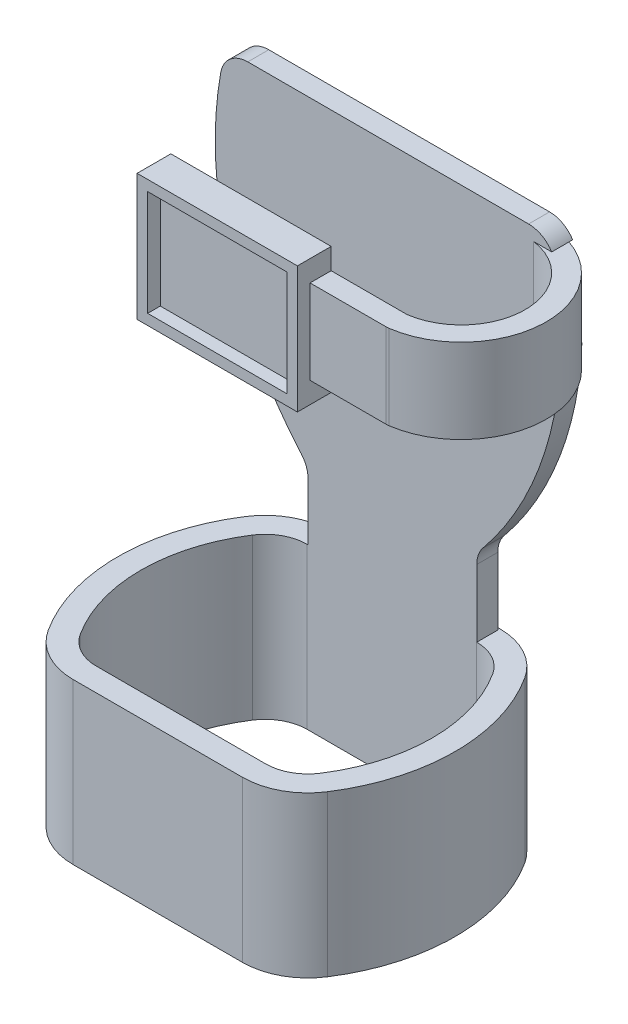
SolidWorks part; units mm, degrees
ref_plane "Alzado" through (0, 0, 0) normal (0, 0, 1) x (1, 0, 0)
ref_plane "Planta" through (0, 0, 0) normal (0, 1, 0) x (1, 0, 0)
ref_plane "Vista lateral" through (0, 0, 0) normal (1, 0, 0) x (0, 0, -1)
sketch "Croquis1" plane through (0, 0, 0) normal (0, 0, 1) x (1, 0, 0)
  line L0 (-15.4785, 127) -> (53.4785, 127)
  line L1 (6.5, 0) -> (33.5, 0)
  line L2 (0, 6.5) -> (0, 51.6048)
  line L3 (0, 130) -> (40, 130)
  line L4 (40, 6.5) -> (40, 53.9643)
  line L5 (40, 130) -> (52.2832, 130)
  line L9 (0, 130) -> (-14.2832, 130)
  line L12 (38, 9) -> (35.8, 9)
  line L13 (38, 9) -> (38, 35)
  line L14 (38, 35) -> (35.8, 35)
  line L15 (35.8, 9) -> (35.8, 35)
  line L16 (2, 9) -> (4.2, 9)
  line L17 (2, 9) -> (2, 35)
  line L18 (2, 35) -> (4.2, 35)
  line L19 (4.2, 9) -> (4.2, 35)
  line L20 (-17.6785, 127) -> (-15.4785, 127)
  line L21 (-17.6785, 127) -> (-17.6785, 101)
  line L22 (-17.6785, 101) -> (-15.4785, 101)
  line L23 (-15.4785, 127) -> (-15.4785, 101)
  line L24 (53.4785, 127) -> (55.6785, 127)
  line L25 (53.4785, 127) -> (53.4785, 101)
  line L26 (53.4785, 101) -> (55.6785, 101)
  line L27 (55.6785, 127) -> (55.6785, 101)
  arc A0 (-20.6785, 124.6623) -> (-1.6158, 55.8937) centre (60, 110) ccw
  arc A2 (41.4689, 58.0799) -> (58.6785, 124.6623) centre (-22, 110) ccw
  arc A3 (33.5, 0) -> (40, 6.5) centre (33.5, 6.5) ccw
  arc A4 (6.5, 0) -> (0, 6.5) centre (6.5, 6.5) cw
  arc A5 (58.6785, 124.6623) -> (52.2832, 130) centre (52.2832, 123.5) ccw
  arc A6 (-20.6785, 124.6623) -> (-14.2832, 130) centre (-14.2832, 123.5) cw
  arc A7 (0, 51.6048) -> (-1.6158, 55.8937) centre (-6.5, 51.6048) ccw
  arc A8 (40, 53.9643) -> (41.4689, 58.0799) centre (46.5, 53.9643) cw
  point P9 (40, 0)
  point P16 (0, 0)
  dimension "D3" = 6.5
  dimension "D4" = 6.5
  dimension "D5" = 6.5
  dimension "D1" = 130
  dimension "D2" = 40
  dimension "D6" = 9
  dimension "D7" = 2
  dimension "D8" = 9
  dimension "D9" = 2
  dimension "D10" = 2.2
  dimension "D11" = 2.2
  dimension "D12" = 26
  dimension "D13" = 26
  dimension "D14" = 3
  dimension "D15" = 3
  dimension "D16" = 26
  dimension "D17" = 26
  dimension "D18" = 3
  dimension "D19" = 3
  dimension "D20" = 2.2
  dimension "D21" = 2.2
extrude "Saliente-Extruir2" add sketch "Croquis1" along normal blind 3
sketch "Croquis2" plane through (0, 0, 0) normal (0, 0, -1) x (-1, 0, 0)
  line L0 (-53.4785, 127) -> (15.4785, 127)
  line L1 (-41.5185, 116.3989) -> (4.4815, 116.3989)
  line L2 (-41.5185, 116.3989) -> (-41.5185, 113.3989)
  line L3 (-41.5185, 113.3989) -> (4.4815, 113.3989)
  line L4 (4.4815, 116.3989) -> (4.4815, 113.3989)
  line L5 (-53.4785, 127) -> (-53.4785, 101) construction
  point P8 (-18.5185, 116.3989)
  dimension "D1" = 46
  dimension "D2" = 34.96
  dimension "D3" = 3
extrude "Saliente-Extruir3" add sketch "Croquis2" along normal blind 20 contours L4 L1 L2 L3
sketch "Croquis3" plane through (0, 116.3989, 0) normal (0, 1, 0) x (1, 0, 0)
  line L1 (41.5185, 0) -> (-4.4815, 0) construction
  line L2 (18.5185, 20) -> (18.5185, 0)
  line L3 (41.5185, 20) -> (-4.4815, 20) construction
  line L5 (13.0185, 20) -> (24.0185, 20)
  line L6 (13.0185, 20) -> (13.0185, 15)
  line L7 (13.0185, 15) -> (24.0185, 15)
  line L8 (24.0185, 20) -> (24.0185, 15)
  circle A0 centre (31.5185, 10) radius 8
  circle A1 centre (5.5185, 10) radius 8
  line M6 (41.5185, 20) -> (-4.4815, 20)
  dimension "D1" = 16
  dimension "D2" = 16
  dimension "D3" = 10
  dimension "D4" = 10
  dimension "D5" = 26
  dimension "D6" = 13
  dimension "D7" = 11
  dimension "D8" = 5
  dimension "D9" = 5.5
extrude "Cortar-Extruir1" cut sketch "Croquis3" against normal blind 20 contours A0 | A1 | L8 L2 L7 M6 | L6 L7 L2 M6
sketch "Croquis5" plane through (0, 0, 0) normal (0, -1, 0) x (1, 0, 0)
  line L0 (39.9643, 63) -> (-0.1889, 63)
  line L23 (44.8877, 58) -> (-5.1123, 58)
  line L27 (39.9643, 8) -> (-0.1889, 8)
  line L29 (39.9643, 58) -> (-0.1889, 58)
  line L30 (39.9643, 3) -> (-0.1889, 3)
  arc A0 (48.3643, 12.574) -> (48.3643, 53.426) centre (16.743, 33) ccw
  arc A1 (-8.5888, 12.574) -> (-8.5888, 53.426) centre (23.0325, 33) cw
  arc A2 (-0.1889, 8) -> (-8.5888, 12.574) centre (-0.1889, 18) cw
  arc A3 (-0.1889, 58) -> (-8.5888, 53.426) centre (-0.1889, 48) ccw
  arc A4 (48.3643, 53.426) -> (39.9643, 58) centre (39.9643, 48) ccw
  arc A5 (39.9643, 8) -> (48.3643, 12.574) centre (39.9643, 18) ccw
  arc A6 (-0.1889, 63) -> (-12.7888, 56.139) centre (-0.1889, 48) ccw
  arc A7 (-12.7888, 9.861) -> (-12.7888, 56.139) centre (23.0325, 33) cw
  arc A8 (-0.1889, 3) -> (-12.7888, 9.861) centre (-0.1889, 18) cw
  arc A9 (39.9643, 3) -> (52.5642, 9.861) centre (39.9643, 18) ccw
  arc A10 (52.5642, 9.861) -> (52.5642, 56.139) centre (16.743, 33) ccw
  arc A11 (52.5642, 56.139) -> (39.9643, 63) centre (39.9643, 48) ccw
  dimension "D1" = 10
  dimension "D2" = 5
extrude "Saliente-Extruir5" add sketch "Croquis5" against normal up to vertex (53.9643 mm away)
sketch "Croquis6" plane through (0, 0, 63) normal (0, 0, 1) x (1, 0, 0)
  line L0 (-0.1889, 38) -> (39.9643, 38)
  line L1 (-0.1889, 53.9643) -> (-0.1889, 0) construction
  line L2 (39.9643, 53.9643) -> (39.9643, 0) construction
  line L3 (-0.1889, 38) -> (-65.1402, 38)
  line L4 (4.2, 9) -> (4.2, 35)
  line L5 (4.2, 35) -> (2, 35)
  line L6 (2, 35) -> (2, 9)
  line L7 (2, 9) -> (4.2, 9)
  line L8 (4.2, 9) -> (4.2, 35)
  line L9 (4.2, 35) -> (2, 35)
  line L10 (2, 35) -> (2, 9)
  line L11 (2, 9) -> (4.2, 9)
  line L12 (35.8, 9) -> (38, 9)
  line L13 (38, 9) -> (38, 35)
  line L14 (38, 35) -> (35.8, 35)
  line L15 (35.8, 35) -> (35.8, 9)
  line L16 (35.8, 9) -> (38, 9)
  line L17 (38, 9) -> (38, 35)
  line L18 (38, 35) -> (35.8, 35)
  line L19 (35.8, 35) -> (35.8, 9)
  line L21 (-65.1402, 38) -> (86.0115, 38)
  line L22 (-65.1402, 38) -> (-65.1402, 58.0527)
  line L23 (-65.1402, 58.0527) -> (86.0115, 58.0527)
  line L24 (86.0115, 38) -> (86.0115, 58.0527)
  line M11 (39.9643, 0) -> (39.9643, 53.9643)
  line M12 (39.9643, 53.9643) -> (-0.1889, 53.9643)
  line M13 (-0.1889, 53.9643) -> (-0.1889, 0)
  dimension "D3" = 3
  dimension "D1" = 0
  dimension "D2" = 0
extrude "Cortar-Extruir2" cut sketch "Croquis6" against normal up to vertex contours L21 L24 L23 L22 L3 M13 M12 M11 | L0 M13 M11 M12
sketch "Croquis7" plane through (53.4785, 0, 0) normal (1, 0, 0) x (0, 0, -1)
  line L1 (0, 127) -> (-33, 127)
  line L2 (0, 127) -> (0, 107)
  line L3 (0, 107) -> (-33, 107)
  line L4 (-33, 127) -> (-33, 107)
  line L5 (-33, 107) -> (-38, 107)
  line L6 (-33, 107) -> (-33, 127)
  line L7 (-33, 127) -> (-38, 127)
  line L8 (-38, 107) -> (-38, 127)
  dimension "D1" = 33
  dimension "D2" = 5
  dimension "D3" = 20
extrude "Saliente-Extruir7" add sketch "Croquis7" against normal blind 33 separate body contours L8 L5 L4 L7
sketch "Croquis9" plane through (0, 0, 38) normal (0, 0, 1) x (1, 0, 0)
  line L0 (20.4785, 107) -> (20.4785, 127) construction
  line L1 (5.4785, 102) -> (35.4785, 102)
  line L2 (5.4785, 102) -> (5.4785, 132)
  line L3 (5.4785, 132) -> (35.4785, 132)
  line L4 (35.4785, 102) -> (35.4785, 132)
  line L5 (5.4785, 102) -> (35.4785, 132) construction
  line L6 (5.4785, 132) -> (35.4785, 102) construction
  point P0 (20.4785, 117)
  dimension "D1" = 30
  dimension "D2" = 30
extrude "Saliente-Extruir8" add sketch "Croquis9" against normal up to vertex
sketch "Croquis10" plane through (0, 127, 0) normal (0, 1, 0) x (1, 0, 0)
  line L2 (53.4785, -33) -> (53.4785, -3)
  line L5 (54.1891, -37.9492) -> (53.4785, -38)
  line L8 (53.4785, -3) -> (53.4785, 0)
  line L12 (53.4785, -33) -> (53.4785, -36)
  line L16 (53.4785, -33) -> (53.4785, 0)
  line L20 (54.1891, 1.9492) -> (53.4785, 2)
  line L21 (53.4785, 2) -> (51.4785, 2)
  line L23 (53.4785, 0) -> (51.4785, 0)
  line L24 (51.4785, 2) -> (51.4785, 0)
  arc A0 (53.4785, -33) -> (53.4785, -3) centre (51.3246, -18) ccw
  arc A1 (54.1891, -37.9492) -> (54.1891, 1.9492) centre (51.3246, -18) ccw
  line M11 (53.4785, -38) -> (53.4785, -33)
  dimension "D4" = 2
  dimension "D5" = 2
  dimension "D2" = 5
extrude "Saliente-Extruir9" add sketch "Croquis10" against normal up to vertex contours L5 A1 L20 L21 L24 L23 L8 A0 M11
sketch "Croquis11" plane through (0, 0, 0) normal (0, 0, -1) x (-1, 0, 0)
  line L1 (17.6785, 127) -> (-55.6785, 127)
  line L2 (17.6785, 127) -> (17.6785, 101)
  line L3 (17.6785, 101) -> (-55.6785, 101)
  line L4 (-55.6785, 127) -> (-55.6785, 101)
  line L5 (-2, 35) -> (-38, 35)
  line L6 (-2, 35) -> (-2, 9)
  line L7 (-2, 9) -> (-38, 9)
  line L8 (-38, 35) -> (-38, 9)
extrude "Saliente-Extruir10" add sketch "Croquis11" against normal up to vertex
sketch "Croquis12" plane through (0, 0, 38) normal (0, 0, 1) x (1, 0, 0)
  line L0 (5.4785, 102) -> (35.4785, 102) construction
  line L2 (5.4785, 132) -> (5.4785, 102) construction
  circle A0 centre (20.4785, 117) radius 12.5
  circle A1 centre (20.4785, 117) radius 15
  dimension "D1" = 25
  dimension "D2" = 15
  dimension "D3" = 15
  dimension "D4" = 2.5
extrude "Saliente-Extruir13" add sketch "Croquis12" along normal blind 10
fillet "Redondeo1" radius 2 1 edges at (51.4785, 117, -2)
sketch "Croquis13" plane through (0, 0, 0) normal (0, -1, 0) x (1, 0, 0)
  line L14 (39.9643, 3) -> (-0.1889, 3)
  line L18 (39.9643, 53) -> (-0.1889, 53)
  line L34 (-14.2788, 28) -> (-14.6123, 28)
  arc A2 (48.3643, 48.426) -> (39.9643, 53) centre (39.9643, 43) ccw
  arc A3 (-8.5888, 7.574) -> (-8.5888, 48.426) centre (23.0325, 28) cw
  arc A4 (48.3643, 7.574) -> (48.3643, 48.426) centre (16.743, 28) ccw
  arc A5 (-0.1889, 53) -> (-8.5888, 48.426) centre (-0.1889, 43) ccw
  arc A6 (-0.1889, 3) -> (-8.5888, 7.574) centre (-0.1889, 13) cw
  arc A7 (48.3643, 7.574) -> (39.9643, 3) centre (39.9643, 13) cw
  dimension "D1" = 10
sketch "Croquis14" plane through (0, 38, 0) normal (0, 1, 0) x (1, 0, 0)
  line L0 (44.8877, -3) -> (-5.1123, -3) construction
  line L1 (39.9643, -3) -> (-0.1889, -3)
  line L2 (44.8877, -53) -> (-5.1123, -53) construction
  line L3 (-0.1889, -63) -> (39.9643, -63)
  line L4 (39.9643, -3) -> (0, -3)
  line L5 (0, -3) -> (-0.1889, -3)
  line L7 (39.9643, -3) -> (0, -3)
  line L8 (0, -3) -> (-0.1889, -3)
  line L9 (39.9643, -53) -> (-0.1889, -53)
  line L10 (39.9643, -56) -> (-0.1889, -56)
  line L11 (39.9643, 0) -> (-0.1889, 0)
  arc A0 (44.8877, -53) -> (44.8877, -3) centre (16.743, -28) ccw construction
  arc A1 (48.3643, -48.426) -> (48.3643, -7.574) centre (16.743, -28) ccw
  arc A2 (-5.1123, -3) -> (-5.1123, -53) centre (23.0325, -28) ccw construction
  arc A3 (-8.5888, -7.574) -> (-8.5888, -48.426) centre (23.0325, -28) ccw
  arc A4 (-0.1889, -53) -> (-8.5888, -48.426) centre (-0.1889, -43) cw
  arc A5 (48.3643, -48.426) -> (39.9643, -53) centre (39.9643, -43) cw
  arc A6 (-12.7888, -56.139) -> (-0.1889, -63) centre (-0.1889, -48) ccw
  arc A7 (39.9643, -63) -> (52.5642, -56.139) centre (39.9643, -48) ccw
  arc A8 (52.5642, -56.139) -> (52.5642, -9.861) centre (16.743, -33) ccw
  arc A9 (52.5642, -9.861) -> (39.9643, -3) centre (39.9643, -18) ccw
  arc A10 (-0.1889, -3) -> (-12.7888, -9.861) centre (-0.1889, -18) ccw
  arc A11 (-12.7888, -9.861) -> (-12.7888, -56.139) centre (23.0325, -33) ccw
  arc A12 (-12.7888, -56.139) -> (-0.1889, -63) centre (-0.1889, -48) ccw
  arc A16 (-0.1889, -3) -> (-6.1699, -4.244) centre (-0.1889, -18) ccw
  arc A17 (48.3643, -7.574) -> (39.9643, -3) centre (39.9643, -13) ccw
  arc A18 (-0.1889, -3) -> (-8.5888, -7.574) centre (-0.1889, -13) ccw
  arc A19 (-0.1889, -56) -> (-11.1088, -50.0538) centre (-0.1889, -43) cw
  arc A20 (-11.1088, -5.9462) -> (-11.1088, -50.0538) centre (23.0325, -28) ccw
  arc A21 (-0.1889, 0) -> (-11.1088, -5.9462) centre (-0.1889, -13) ccw
  arc A22 (50.8842, -5.9462) -> (39.9643, 0) centre (39.9643, -13) ccw
  arc A23 (50.8842, -50.0538) -> (50.8842, -5.9462) centre (16.743, -28) ccw
  arc A24 (50.8842, -50.0538) -> (39.9643, -56) centre (39.9643, -43) cw
  dimension "D2" = 10
  dimension "D1" = 0
  dimension "D3" = 3
extrude "Cortar-Extruir4" cut sketch "Croquis14" against normal through all contours A23 A18 A3 L4 L5 A0 A2 A6 A1 A17 A22 | A23 A24 A6 A7 L2 L3 L4 A19 A20 L0 L10 A21
sketch "Croquis16" plane through (0, 38, 0) normal (0, 1, 0) x (1, 0, 0)
  line L0 (44.8877, -3) -> (-5.1123, -3) construction
  line L1 (44.8877, -53) -> (-5.1123, -53) construction
  line L2 (39.9643, -3) -> (-0.1889, -3)
  line L3 (39.9643, -53) -> (-0.1889, -53)
  line L4 (39.9643, 0) -> (-0.1889, 0)
  line L5 (39.9643, -56) -> (-0.1889, -56)
  arc A0 (-5.1123, -3) -> (-5.1123, -53) centre (23.0325, -28) ccw construction
  arc A1 (44.8877, -53) -> (44.8877, -3) centre (16.743, -28) ccw construction
  arc A2 (-8.5888, -7.574) -> (-8.5888, -48.426) centre (23.0325, -28) ccw
  arc A3 (48.3643, -48.426) -> (48.3643, -7.574) centre (16.743, -28) ccw
  arc A4 (-8.5888, -48.426) -> (-0.1889, -53) centre (-0.1889, -43) ccw
  arc A5 (48.3643, -48.426) -> (39.9643, -53) centre (39.9643, -43) cw
  arc A6 (39.9643, -3) -> (48.3643, -7.574) centre (39.9643, -13) cw
  arc A7 (-0.1889, -3) -> (-8.5888, -7.574) centre (-0.1889, -13) ccw
  arc A8 (-0.1889, 0) -> (-11.1088, -5.9462) centre (-0.1889, -13) ccw
  arc A9 (-11.1088, -5.9462) -> (-11.1088, -50.0538) centre (23.0325, -28) ccw
  arc A10 (-11.1088, -50.0538) -> (-0.1889, -56) centre (-0.1889, -43) ccw
  arc A11 (50.8842, -50.0538) -> (39.9643, -56) centre (39.9643, -43) cw
  arc A12 (50.8842, -50.0538) -> (50.8842, -5.9462) centre (16.743, -28) ccw
  arc A13 (39.9643, 0) -> (50.8842, -5.9462) centre (39.9643, -13) cw
  dimension "D1" = 10
  dimension "D2" = 3
extrude "Saliente-Extruir15" add sketch "Croquis16" against normal up to vertex (38 mm away)
sketch "Croquis17" plane through (0, 0, -20) normal (0, 0, -1) x (-1, 0, 0)
  line L1 (4.4815, 113.3989) -> (-41.5185, 113.3989)
  line L2 (4.4815, 113.3989) -> (4.4815, 116.3989)
  line L3 (4.4815, 116.3989) -> (-41.5185, 116.3989)
  line L4 (-41.5185, 113.3989) -> (-41.5185, 116.3989)
extrude "Cortar-Extruir5" cut sketch "Croquis17" against normal up to vertex (20 mm away)
sketch "Croquis18" plane through (0, 0, 48) normal (0, 0, 1) x (1, 0, 0)
  line L1 (-9.7168, 146.6646) -> (48.6312, 146.6646)
  line L2 (-9.7168, 146.6646) -> (-9.7168, 90.9274)
  line L3 (-9.7168, 90.9274) -> (48.6312, 90.9274)
  line L4 (48.6312, 146.6646) -> (48.6312, 90.9274)
extrude "Cortar-Extruir6" cut sketch "Croquis18" against normal up to vertex (10 mm away)
sketch "Croquis20" plane through (0, 0, 38) normal (0, 0, 1) x (1, 0, 0)
  line L0 (53.4785, 107) -> (53.4785, 127) construction
  line L1 (32.9785, 129.5) -> (-0.0215, 129.5)
  line L2 (32.9785, 129.5) -> (32.9785, 104.5)
  line L3 (32.9785, 104.5) -> (-0.0215, 104.5)
  line L5 (35.4785, 127) -> (35.4785, 132) construction
  line L6 (35.4785, 132) -> (5.4785, 132) construction
  line L7 (5.4785, 102) -> (35.4785, 102) construction
  line L8 (35.4785, 132) -> (35.4785, 102)
  line L9 (35.4785, 102) -> (-2.5215, 102)
  line L10 (-2.5215, 132) -> (-2.5215, 102)
  line L11 (35.4785, 132) -> (-2.5215, 132)
  line L12 (-0.0215, 129.5) -> (-0.0215, 104.5) construction
  point P4 (32.9785, 117)
  point P7 (53.4785, 117)
  line M5 (5.4785, 132) -> (5.4785, 102)
  dimension "D1" = 33
  dimension "D2" = 25
  dimension "D3" = 0
  dimension "D4" = 2.5
  dimension "D5" = 2.5
  dimension "D6" = 2.5
  dimension "D7" = 2.5
extrude "Saliente-Extruir16" add sketch "Croquis20" against normal up to vertex contours L1 L12 L3 M5 | L12 L1 L11 L10 L9 L3 M5
sketch "Croquis21" plane through (0, 0, 38) normal (0, 0, 1) x (1, 0, 0)
  line L0 (-0.0215, 129.5) -> (-0.0215, 104.5)
  line L1 (-2.5215, 132) -> (35.4785, 132)
  line L2 (-2.5215, 132) -> (-2.5215, 102)
  line L3 (-2.5215, 102) -> (35.4785, 102)
  line L4 (35.4785, 132) -> (35.4785, 102)
  line L5 (-0.0215, 104.5) -> (32.9785, 104.5)
  line L6 (32.9785, 129.5) -> (32.9785, 104.5)
  line L7 (-0.0215, 129.5) -> (32.9785, 129.5)
  dimension "D1" = 2.5
extrude "Saliente-Extruir17" add sketch "Croquis21" along normal blind 3
sketch "Croquis22" plane through (0, 0, 0) normal (0, -1, 0) x (1, 0, 0)
  line L0 (-0.1889, -2.5) -> (39.9643, -2.5)
  line L1 (39.9643, 58.5) -> (-0.1889, 58.5)
  line L2 (-0.1889, 0) -> (39.9643, 0)
  line L3 (39.9643, 56) -> (-0.1889, 56)
  line L4 (-0.1889, 0) -> (39.9643, 0)
  line L5 (39.9643, 56) -> (-0.1889, 56)
  arc A0 (-0.1889, 58.5) -> (-13.2088, 51.4103) centre (-0.1889, 43) ccw
  arc A1 (-13.2088, 51.4103) -> (-13.2088, 4.5897) centre (23.0325, 28) ccw
  arc A2 (-13.2088, 4.5897) -> (-0.1889, -2.5) centre (-0.1889, 13) ccw
  arc A3 (39.9643, -2.5) -> (52.9842, 4.5897) centre (39.9643, 13) ccw
  arc A4 (52.9842, 4.5897) -> (52.9842, 51.4103) centre (16.743, 28) ccw
  arc A5 (52.9842, 51.4103) -> (39.9643, 58.5) centre (39.9643, 43) ccw
  arc A6 (-0.1889, 56) -> (-11.1088, 50.0538) centre (-0.1889, 43) ccw
  arc A7 (-11.1088, 50.0538) -> (-11.1088, 5.9462) centre (23.0325, 28) ccw
  arc A8 (-11.1088, 5.9462) -> (-0.1889, 0) centre (-0.1889, 13) ccw
  arc A9 (39.9643, 0) -> (50.8842, 5.9462) centre (39.9643, 13) ccw
  arc A10 (50.8842, 5.9462) -> (50.8842, 50.0538) centre (16.743, 28) ccw
  arc A11 (50.8842, 50.0538) -> (39.9643, 56) centre (39.9643, 43) ccw
  arc A12 (-0.1889, 56) -> (-11.1088, 50.0538) centre (-0.1889, 43) ccw
  arc A13 (-11.1088, 50.0538) -> (-11.1088, 5.9462) centre (23.0325, 28) ccw
  arc A14 (-11.1088, 5.9462) -> (-0.1889, 0) centre (-0.1889, 13) ccw
  arc A15 (39.9643, 0) -> (50.8842, 5.9462) centre (39.9643, 13) ccw
  arc A16 (50.8842, 5.9462) -> (50.8842, 50.0538) centre (16.743, 28) ccw
  arc A17 (50.8842, 50.0538) -> (39.9643, 56) centre (39.9643, 43) ccw
  dimension "D1" = 0
  dimension "D2" = 2.5
extrude "Saliente-Extruir18" add sketch "Croquis22" against normal up to vertex (38 mm away) up to point (-11.1088, 38, 5.9462)
sketch "Croquis23" plane through (0, 0, 0) normal (0, 0, -1) x (-1, 0, 0)
  line L7 (-40, 38) -> (0, 38)
  line L8 (0, 38) -> (0, 51.6048)
  line L9 (14.2832, 130) -> (-52.2832, 130)
  line L10 (-57.7605, 127) -> (-51.4785, 127)
  line L11 (-51.4785, 127) -> (-51.4785, 107)
  line L12 (-51.4785, 107) -> (-59.9451, 107)
  line L13 (-40, 53.9643) -> (-40, 38)
  line L14 (-40, 38) -> (0, 38)
  line L15 (0, 38) -> (0, 51.6048)
  line L16 (14.2832, 130) -> (-52.2832, 130)
  line L17 (-57.7605, 127) -> (-51.4785, 127)
  line L18 (-51.4785, 127) -> (-51.4785, 107)
  line L19 (-51.4785, 107) -> (-59.9451, 107)
  line L20 (-40, 53.9643) -> (-40, 38)
  arc A6 (1.6158, 55.8937) -> (0, 51.6048) centre (6.5, 51.6048) ccw
  arc A7 (1.6158, 55.8937) -> (20.6785, 124.6623) centre (-60, 110) ccw
  arc A8 (20.6785, 124.6623) -> (14.2832, 130) centre (14.2832, 123.5) ccw
  arc A9 (-52.2832, 130) -> (-57.7605, 127) centre (-52.2832, 123.5) ccw
  arc A10 (-59.9451, 107) -> (-41.4689, 58.0799) centre (22, 110) ccw
  arc A11 (-40, 53.9643) -> (-41.4689, 58.0799) centre (-46.5, 53.9643) ccw
  arc A12 (1.6158, 55.8937) -> (0, 51.6048) centre (6.5, 51.6048) ccw
  arc A13 (1.6158, 55.8937) -> (20.6785, 124.6623) centre (-60, 110) ccw
  arc A14 (20.6785, 124.6623) -> (14.2832, 130) centre (14.2832, 123.5) ccw
  arc A15 (-52.2832, 130) -> (-57.7605, 127) centre (-52.2832, 123.5) ccw
  arc A16 (-59.9451, 107) -> (-41.4689, 58.0799) centre (22, 110) ccw
  arc A17 (-40, 53.9643) -> (-41.4689, 58.0799) centre (-46.5, 53.9643) ccw
  dimension "D1" = 0
extrude "Saliente-Extruir19" add sketch "Croquis23" along normal up to vertex (1.9746 mm away)
